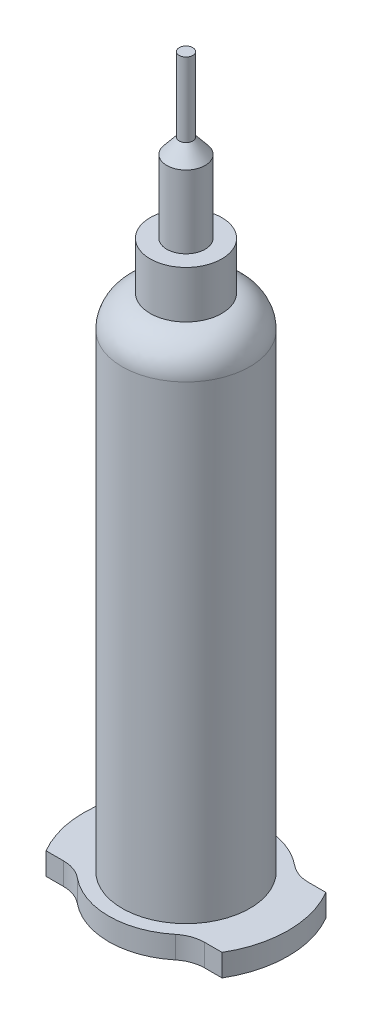
SolidWorks part; units mm, degrees
ref_plane "Front Plane" through (0, 0, 0) normal (0, 0, 1) x (1, 0, 0)
ref_plane "Top Plane" through (0, 0, 0) normal (0, 1, 0) x (1, 0, 0)
ref_plane "Right Plane" through (0, 0, 0) normal (1, 0, 0) x (0, 0, -1)
ref_axis "Axis1" through (-33.0333, 0, 0) along (1, 0, 0)
ref_axis "Axis2" through (0, 24.5224, 0) along (0, -1, 0)
ref_axis "Axis3" through (0, 0, -52.9538) along (0, 0, 1)
sketch "Sketch2" plane through (0, 0, 0) normal (0, 0, 1) x (1, 0, 0)
  line L8 (0, 54.38) -> (0, -54.38)
  line L9 (0, 54.38) -> (1, 54.38)
  line L10 (1, 54.38) -> (1, 43.03)
  line L11 (1, 43.03) -> (2.825, 40.74)
  line L12 (2.825, 40.74) -> (2.825, 29.62)
  line L13 (2.825, 29.62) -> (5.275, 29.62)
  line L14 (5.275, 29.62) -> (5.275, 22.38)
  line L15 (5.275, 22.38) -> (9.4, 22.38)
  line L16 (9.4, 22.38) -> (9.4, -54.38)
  line L17 (9.4, -54.38) -> (0, -54.38)
  point P2 (0, 0)
  dimension "D2" = 1
  dimension "D3" = 11.35
  dimension "D4" = 2.825
  dimension "D5" = 5.275
  dimension "D6" = 9.4
  dimension "D7" = 32
  dimension "D8" = 24.76
  dimension "D9" = 2.29
  dimension "D11" = 76.76
revolve "Revolve1" add sketch "Sketch2" angle 360 about axis through (0, 24.5224, 0) along (0, -1, 0) region at (4.3954, -10.7961, 0)
fillet "Fillet1" radius 5 1 edges at (0, 22.38, 9.4)
sketch "Sketch4" plane through (0, -54.38, 0) normal (0, -1, 0) x (1, 0, 0)
  line L2 (-12.9607, 7.65) -> (-10.398, 7.65)
  line L5 (10.398, 7.65) -> (12.9607, 7.65)
  line L8 (-12.9607, -7.65) -> (-10.398, -7.65)
  line L9 (10.398, -7.65) -> (12.9607, -7.65)
  line L10 (-8.4183, 7.65) -> (-8.4183, -7.65) construction
  line L11 (8.4183, 7.65) -> (8.4183, -7.65) construction
  line L12 (-8.4183, 0) -> (8.4183, 0) construction
  arc A2 (-7.223, -8.7874) -> (7.223, -8.7874) centre (0, 0) ccw
  arc A3 (-12.9607, 7.65) -> (-12.9607, -7.65) centre (0, 0) ccw
  arc A4 (12.9607, -7.65) -> (12.9607, 7.65) centre (0, 0) ccw
  arc A5 (7.223, 8.7874) -> (-7.223, 8.7874) centre (0, 0) ccw
  arc A6 (-10.398, -7.65) -> (-7.223, -8.7874) centre (-10.398, -12.65) cw
  arc A7 (10.398, -7.65) -> (7.223, -8.7874) centre (10.398, -12.65) ccw
  arc A8 (10.398, 7.65) -> (7.223, 8.7874) centre (10.398, 12.65) cw
  arc A9 (-10.398, 7.65) -> (-7.223, 8.7874) centre (-10.398, 12.65) ccw
  point P14 (0, 0)
  dimension "D1" = 22.75
  dimension "D2" = 30.1
  dimension "D3" = 15.3
  dimension "D4" = 5
extrude "Boss-Extrude1" add sketch "Sketch4" along normal blind 3.4
scale "Scale1" scale about origin uniform scaling no x scale factor 1.05 y scale factor 1.01 z scale factor 1.05
